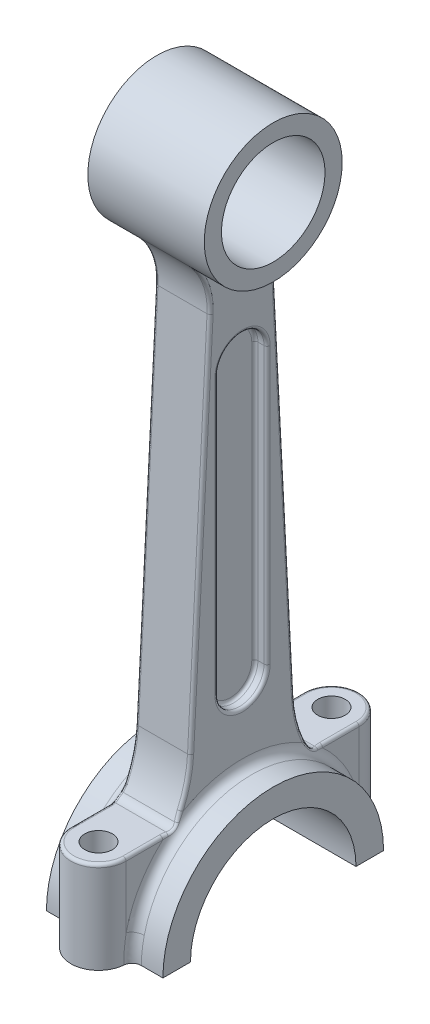
SolidWorks part; units mm, degrees
ref_plane "Front Plane" through (0, 0, 0) normal (0, 0, 1) x (1, 0, 0)
ref_plane "Top Plane" through (0, 0, 0) normal (0, 1, 0) x (1, 0, 0)
ref_plane "Right Plane" through (0, 0, 0) normal (1, 0, 0) x (0, 0, -1)
sketch "Sketch1" plane through (0, 0, 0) normal (1, 0, 0) x (0, 0, -1)
  line L0 (0, 0) -> (0, -179840.3393) construction
  line L1 (0, 0) -> (179840.3393, 0) construction
  line L2 (10, -20.1556) -> (16.9576, -152.9141)
  line L3 (-10, -20.1556) -> (-16.9576, -152.9141)
  line L4 (-47, -201.2) -> (47, -201.2)
  line L5 (47, -201.2) -> (47, -171.2)
  line L6 (47, -171.2) -> (19.8997, -171.2)
  line L7 (-47, -201.2) -> (-47, -171.2)
  line L8 (-47, -171.2) -> (-19.8997, -171.2)
  line L9 (0, -50) -> (0, -140) construction
  line L10 (8, -50) -> (8, -140)
  line L11 (-8, -50) -> (-8, -140)
  circle A0 centre (0, 0) radius 22.5
  circle A1 centre (0, 0) radius 16.9
  arc A2 (36, -201.2) -> (-36, -201.2) centre (0, -201.2) ccw
  arc A3 (27, -201.2) -> (-27, -201.2) centre (0, -201.2) ccw
  arc A4 (16.9576, -152.9141) -> (26.9539, -177.3361) centre (56.9028, -150.8207) ccw
  arc A5 (8, -50) -> (-8, -50) centre (0, -50) ccw
  arc A6 (-16.9576, -152.9141) -> (-26.9539, -177.3361) centre (-56.9028, -150.8207) cw
  arc A7 (-8, -140) -> (8, -140) centre (0, -140) ccw
  point P25 (0, -201.2)
  point P30 (0, -95)
  dimension "D1" = 45
  dimension "D2" = 33.8
  dimension "D3" = 27
  dimension "D4" = 36
  dimension "D7" = 40
  dimension "D14" = 50
  dimension "D12" = 8
  dimension "D5" = 201.2
  dimension "D6" = 20
  dimension "D8" = 6
  dimension "D9" = 94
  dimension "D10" = 30
  dimension "D11" = 30
  dimension "D13" = 90
extrude "Boss-Extrude1" add sketch "Sketch1" along normal mid plane 38 contours A0 A1 | A3 L4 A2 region at (0, -21.8636, 0) region at (0, -174.6454, -23.0986)
extrude "Boss-Extrude2" add sketch "Sketch1<3>" along normal mid plane 18 contours L6 A4 A2 L4 L5 | A4 L6 A2 | L8 A6 A2 | A6 L8 L7 L4 A2 region at (0, -172.7087, -22.6888) region at (0, -183.9384, -38.6271) region at (0, -183.9384, 38.6271) region at (0, -172.7087, 22.6888)
sketch "Sketch1<3>" plane through (0, 0, 0) normal (1, 0, 0) x (0, 0, -1) same geometry as "Sketch1"
extrude "Boss-Extrude3" add sketch "Sketch1<4>" along normal mid plane 18 contours L3 A6 L8 A2 L6 A4 L2 A0 A7 L11 A5 L10 region at (0, -86.6174, -11.905)
sketch "Sketch1<4>" plane through (0, 0, 0) normal (1, 0, 0) x (0, 0, -1) same geometry as "Sketch1"
extrude "Boss-Extrude4" add sketch "Sketch1<5>" along normal mid plane 10 contours L11 A7 L10 A5 region at (0, -95, 0)
sketch "Sketch1<5>" plane through (0, 0, 0) normal (1, 0, 0) x (0, 0, -1) same geometry as "Sketch1"
fillet "Fillet1" radius 22.5 2 edges at (0, -20.1556, 10) (0, -20.1556, -10)
fillet "Fillet2" radius 1 16 edges at (-9, -42, 0) (-9, -95, -8) (-9, -148, 0) (9, -42, 0) (9, -95, -8) (9, -148, 0) (-9, -95, 8) (9, -95, 8) (5, -42, 0) (5, -95, -8) (5, -148, 0) (5, -95, 8) (-5, -148, 0) (-5, -95, -8) (-5, -42, 0) (-5, -95, 8)
fillet "Fillet3" 2 edges at (-9, -186.2, 47) (9, -186.2, 47) type full round first side face at (-9, -95, 0) second side face at (9, -95, 0) middle face at (0, -186.2, 47)
fillet "Fillet4" 2 edges at (-9, -186.2, -47) (9, -186.2, -47) type full round first side face at (-9, -95, 0) second side face at (9, -95, 0) middle face at (0, -186.2, -47)
hole_wizard "Ø1.0mm Dowel Hole1" positions "3DSketch1" profile "Sketch3" hole size "Ø1.0" standard "ANSI Metric" end condition up to next
sketch3d "3DSketch1"
  line L0 (0, -201.2, 38) -> (0, -171.2, 38) construction
  line L1 (0, -201.2, -38) -> (0, -171.2, -38) construction
  point P0 (0, -201.2, 38)
  point P4 (0, -201.2, -38)
sketch "Sketch3" plane through (0, -201.2, 38) normal (1, 0, 0) x (0, 0, -1)
  line L0 (0, 0) -> (0, 30)
  line L1 (0, 30) -> (4.5, 30)
  line L2 (4.5, 30) -> (4.5, 0)
  line L5 (4.5, 0) -> (0, 0)
  line L11 (0, -6.35) -> (0, 107.95) construction
  dimension "Thru Hole Dia." = 9
  dimension "Thru Hole Depth" = 30
fillet "Fillet5" radius 3 2 edges at (-9, -165.2, 0) (9, -165.2, 0)
fillet "Fillet6" radius 3 2 edges at (0, -171.2, -22.4835) (0, -171.2, 22.4835)
fillet "Fillet7" radius 1 16 edges at (9, -22.8752, -11.9103) (0, -171.2, -47) (9, -171.2, -31.4599) (9.1907, -170.5483, -22.3715) (9, -160.7968, -18.1668) (9, -22.8752, 11.9103) (0, -171.2, 47) (9, -171.2, 31.4599) (9.1676, -170.9257, 22.9851) (9, -160.7968, 18.1668) (9, -92.303, -13.7811) (9, -92.303, 13.7811)
